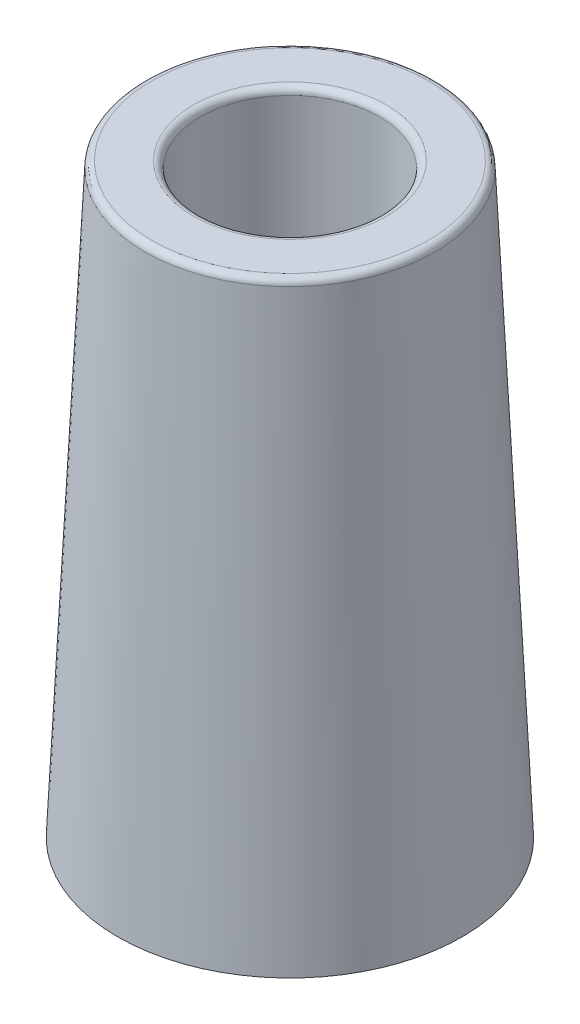
SolidWorks part; units mm, degrees
ref_plane "Front Plane" through (0, 0, 0) normal (0, 0, 1) x (1, 0, 0)
ref_plane "Top Plane" through (0, 0, 0) normal (0, 1, 0) x (1, 0, 0)
ref_plane "Right Plane" through (0, 0, 0) normal (1, 0, 0) x (0, 0, -1)
sketch "Sketch1" plane through (0, 0, 0) normal (0, 1, 0) x (1, 0, 0)
  line L0 (0, 0) -> (0, 25) construction
  circle A0 centre (0, 0) radius 25
  dimension "D1" = 50
extrude "Boss-Extrude1" [suppressed] add sketch "Sketch1" along normal blind 85 draft 2.5
sketch "Sketch2" [suppressed] plane through (0, 85, 0) normal (0, 1, 0) x (1, 0, 0)
  circle A0 centre (0, 0) radius 13
  dimension "D1" = 26
extrude "Cut-Extrude1" [suppressed] cut sketch "Sketch2" against normal offset from surface (80 mm away) 5
fillet "Fillet1" [suppressed] radius 2
ref_plane "Plane1" through (0, 85, 0) normal (0, 1, 0) x (1, 0, 0)
sketch "Sketch3" plane through (0, 85, 0) normal (0, 1, 0) x (1, 0, 0)
  line L0 (0, 0) -> (0, 21) construction
  circle A0 centre (0, 0) radius 13 construction
  circle A1 centre (0, 0) radius 21
  dimension "D1" = 26
  dimension "D2" = 8
loft "Loft1" add profiles "Sketch3", "Sketch1<3>" connector at (0, 85, -21) connector at (0, 0, -25)
sketch "Sketch1<3>" plane through (0, 0, 0) normal (0, 1, 0) x (1, 0, 0) same geometry as "Sketch1"
sketch "Sketch4" plane through (0, 85, 0) normal (0, 1, 0) x (1, 0, 0)
  circle A0 centre (0, 0) radius 13
  dimension "D1" = 26
extrude "Cut-Extrude2" cut sketch "Sketch4" against normal offset from surface (81 mm away) 4 up to face at (0, 0, 25)
fillet "Fillet2" radius 1 2 edges at (0, 85, 21) (0, 85, 13)
